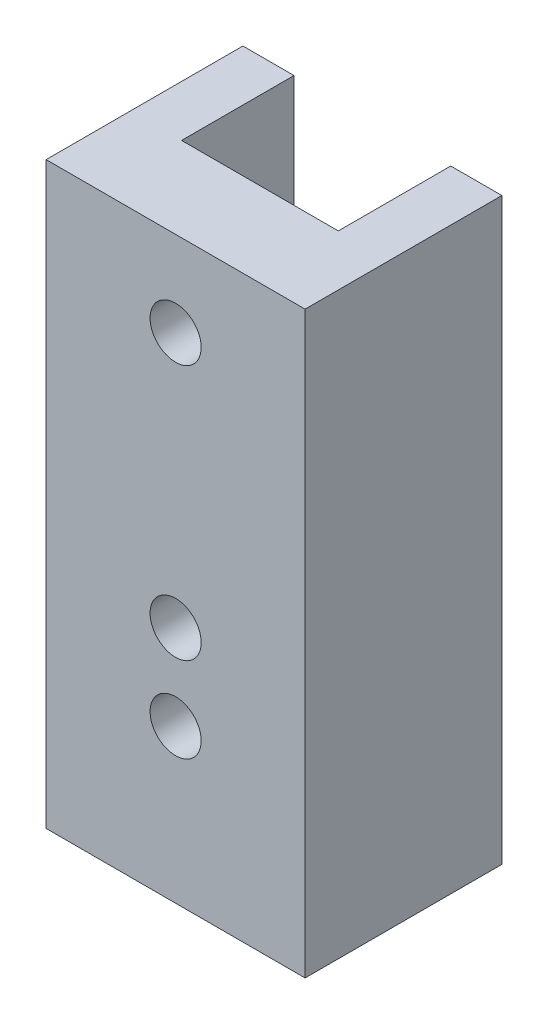
SolidWorks part; units mm, degrees
ref_plane "Front Plane" through (0, 0, 0) normal (0, 0, 1) x (1, 0, 0)
ref_plane "Top Plane" through (0, 0, 0) normal (0, 1, 0) x (1, 0, 0)
ref_plane "Right Plane" through (0, 0, 0) normal (1, 0, 0) x (0, 0, -1)
sketch "Sketch1" plane through (0, 0, 0) normal (0, 1, 0) x (1, 0, 0)
  line L0 (4.6, 3.25) -> (4.6, -3.35)
  line L1 (-4.6, 3.25) -> (4.6, 3.25)
  line L5 (4.6, 3.25) -> (7.6, 3.25)
  line L6 (7.6, 3.25) -> (7.6, -8.3)
  line L7 (-4.6, -3.35) -> (4.6, -3.35)
  line L8 (-4.6, 3.25) -> (-4.6, -3.35)
  line L10 (-4.6, 3.35) -> (4.6, 3.35) construction
  line L11 (-4.5, 3.25) -> (4.5, 3.25) construction
  line L12 (7.6, -8.3) -> (-7.6, -8.3)
  line L13 (-4.6, 3.35) -> (-4.6, -3.35) construction
  line L14 (4.6, 3.35) -> (4.6, -3.35) construction
  line L15 (4.5, 3.25) -> (4.5, -3.25) construction
  line L16 (-4.5, -3.25) -> (4.5, -3.25) construction
  line L17 (-4.5, 3.25) -> (-4.5, -3.25) construction
  line L18 (0, -8.3) -> (0, -6.0345)
  line L19 (-7.6, 3.25) -> (-7.6, -8.3)
  line L20 (-4.6, 3.25) -> (-7.6, 3.25)
  point P0 (0, 0)
  dimension "D1" = 0.1
extrude "Boss-Extrude1" add sketch "Sketch1" along normal blind 34 contours L8 L20 L19 L12 L6 L5 L0 L7 region at (0, 0, 3.8336)
sketch "Sketch2" plane through (0, 0, 8.3) normal (0, 0, 1) x (1, 0, 0)
  line L0 (0, 0) -> (0, 9)
  line L1 (7.6, 0) -> (-7.6, 0) construction
  circle A0 centre (0, 9) radius 1.5
  circle A1 centre (0, 29) radius 1.5
  dimension "D1" = 2
extrude "Cut-Extrude1" cut sketch "Sketch2" against normal blind 34 contours A0 | A1 region at (1.0307, 7.9693, 8.3) region at (0, 29, 8.3)
sketch "Sketch3" plane through (0, 0, 8.3) normal (0, 0, 1) x (1, 0, 0)
  line L0 (0, 9) -> (0, 14)
  line L4 (-7.6, 0) -> (7.6, 0)
  line L5 (7.6, 0) -> (7.6, 34)
  line L6 (7.6, 34) -> (-7.6, 34)
  line L7 (-7.6, 34) -> (-7.6, 0)
  line L8 (-7.6, 0) -> (7.6, 0)
  line L9 (7.6, 0) -> (7.6, 34)
  line L10 (7.6, 34) -> (-7.6, 34)
  line L11 (-7.6, 34) -> (-7.6, 0)
  circle A0 centre (0, 14) radius 1.5
  circle A1 centre (0, 29) radius 1.5
  circle A2 centre (0, 29) radius 1.5
  circle A3 centre (0, 9) radius 1.5
  circle A4 centre (0, 9) radius 1.5
  dimension "D1" = 0
  dimension "D2" = 0
  dimension "D3" = 0
extrude "Cut-Extrude2" cut sketch "Sketch3" against normal blind 10 contours A0 region at (-1.0307, 15.0307, 8.3)
